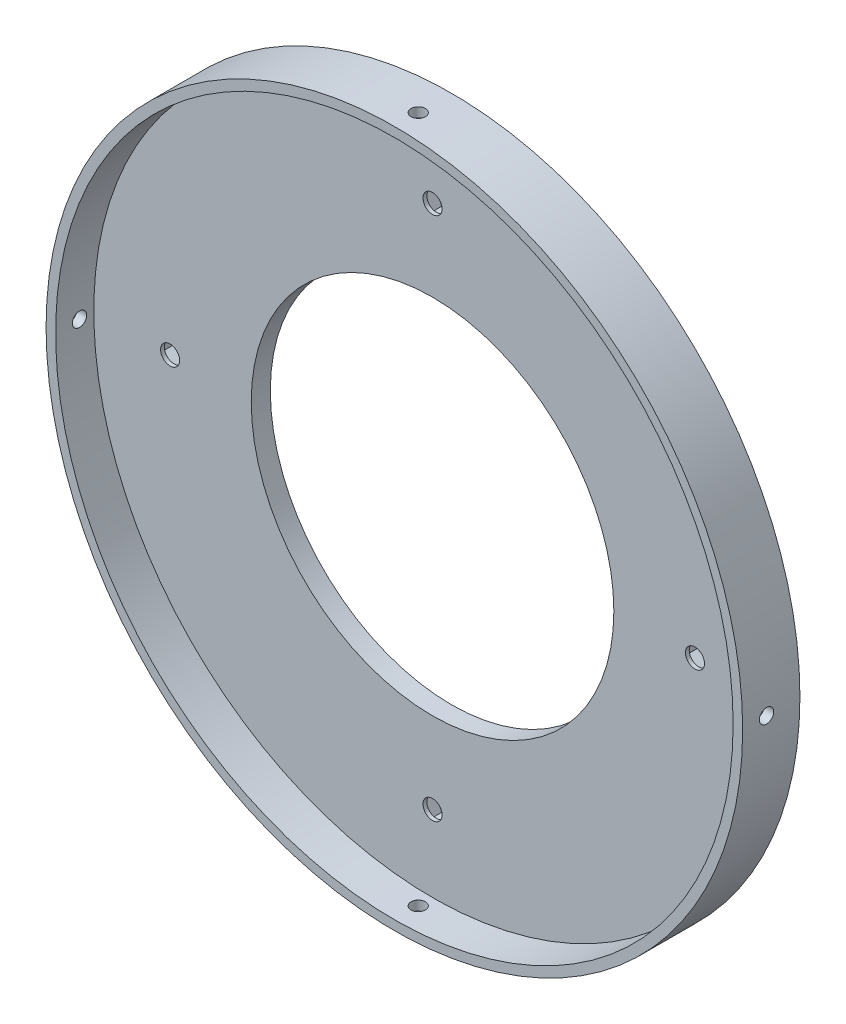
SolidWorks part; units mm, degrees
material "PET"
ref_plane "Front Plane" through (0, 0, 0) normal (0, 0, 1) x (1, 0, 0)
ref_plane "Top Plane" through (0, 0, 0) normal (0, 1, 0) x (1, 0, 0)
ref_plane "Right Plane" through (0, 0, 0) normal (1, 0, 0) x (0, 0, -1)
sketch "Sketch1" plane through (0, 0, 0) normal (0, 0, 1) x (1, 0, 0)
  circle A0 centre (0, 0) radius 73
  circle A1 centre (0, 0) radius 38
  dimension "D1" = 146
  dimension "D2" = 35
extrude "Boss-Extrude1" add sketch "Sketch1" along normal blind 4
sketch "Sketch2" plane through (0, 0, 4) normal (0, 0, 1) x (1, 0, 0)
  circle A0 centre (0, 0) radius 71
  circle A1 centre (0, 0) radius 73
  circle A2 centre (0, 0) radius 73
  dimension "D1" = 0
  dimension "D2" = 2
extrude "Boss-Extrude2" add sketch "Sketch2" along normal blind 8
sketch "Sketch3" plane through (0, 0, 0) normal (0, 1, 0) x (1, 0, 0)
  line L0 (-73, -12) -> (73, -12) construction
  circle A0 centre (0, -7) radius 1.5
  dimension "D2" = 3
  dimension "D1" = 5
extrude "Cut-Extrude1" cut sketch "Sketch3" against normal up to surface (73 mm away) up to face at (73, 0, 0)
pattern_circular "CirPattern1" count 4 over 360 about axis through (0, 0, 4) along (0, 0, -1) of "Cut-Extrude1"
sketch "Sketch9" plane through (0, 0, 0) normal (0, 0, -1) x (-1, 0, 0)
  point P0 (0, 55)
  point P4 (55, 0)
  point P6 (0, -55)
  point P8 (-55, 0)
  dimension "D1" = 55
  dimension "D2" = 0
  dimension "D3" = 55
  dimension "D4" = 55
  dimension "D5" = 55
hole_wizard "Ø4.0mm Dowel Hole1" positions "Sketch9" profile "Sketch10" hole size "Ø4.0" standard "ISO" end condition through all
sketch "Sketch10" plane through (0, 55, 0) normal (1, 0, 0) x (0, 1, 0)
  line L0 (0, 0) -> (0, 12)
  line L1 (0, 12) -> (2, 12)
  line L2 (2, 12) -> (2, 0)
  line L5 (2, 0) -> (0, 0)
  line L11 (0, -6.35) -> (0, 107.95) construction
  dimension "Thru Hole Dia." = 4
  dimension "Thru Hole Depth" = 12
sketch "Sketch13" plane through (0, 0, 0) normal (0, 0, -1) x (-1, 0, 0)
  line L0 (0, 0) -> (55, 0) construction
  line L1 (4.0415, 55) -> (2.0207, 58.5)
  line L2 (2.0207, 58.5) -> (-2.0207, 58.5)
  line L3 (-2.0207, 58.5) -> (-4.0415, 55)
  line L4 (-4.0415, 55) -> (-2.0207, 51.5)
  line L5 (-2.0207, 51.5) -> (2.0207, 51.5)
  line L6 (2.0207, 51.5) -> (4.0415, 55)
  line L7 (55, -4.0415) -> (58.5, -2.0207)
  line L8 (58.5, -2.0207) -> (58.5, 2.0207)
  line L9 (58.5, 2.0207) -> (55, 4.0415)
  line L10 (55, 4.0415) -> (51.5, 2.0207)
  line L11 (51.5, 2.0207) -> (51.5, -2.0207)
  line L12 (51.5, -2.0207) -> (55, -4.0415)
  line L13 (-4.0415, -55) -> (-2.0207, -58.5)
  line L14 (-2.0207, -58.5) -> (2.0207, -58.5)
  line L15 (2.0207, -58.5) -> (4.0415, -55)
  line L16 (4.0415, -55) -> (2.0207, -51.5)
  line L17 (2.0207, -51.5) -> (-2.0207, -51.5)
  line L18 (-2.0207, -51.5) -> (-4.0415, -55)
  line L19 (-55, 4.0415) -> (-58.5, 2.0207)
  line L20 (-58.5, 2.0207) -> (-58.5, -2.0207)
  line L21 (-58.5, -2.0207) -> (-55, -4.0415)
  line L22 (-55, -4.0415) -> (-51.5, -2.0207)
  line L23 (-51.5, -2.0207) -> (-51.5, 2.0207)
  line L24 (-51.5, 2.0207) -> (-55, 4.0415)
  circle A0 centre (0, 55) radius 3.5 construction
  circle A1 centre (55, 0) radius 3.5 construction
  circle A2 centre (0, -55) radius 3.5 construction
  circle A3 centre (-55, 0) radius 3.5 construction
  point P40 (0, 0)
  dimension "D1" = 7
extrude "Cut-Extrude2" cut sketch "Sketch13" against normal blind 3.2
